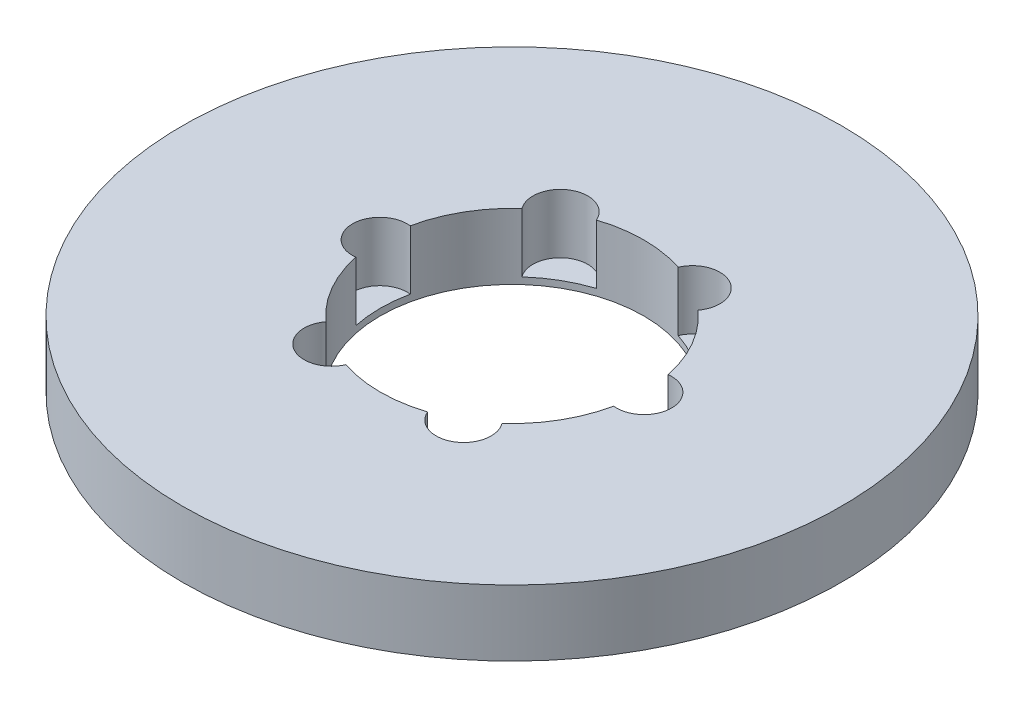
SolidWorks part; units mm, degrees
ref_plane "Front Plane" through (0, 0, 0) normal (0, 0, 1) x (1, 0, 0)
ref_plane "Top Plane" through (0, 0, 0) normal (0, 1, 0) x (1, 0, 0)
ref_plane "Right Plane" through (0, 0, 0) normal (1, 0, 0) x (0, 0, -1)
sketch "Sketch1" plane through (0, 0, 0) normal (0, 1, 0) x (1, 0, 0)
  circle A0 centre (0, 0) radius 75
  dimension "FLANGE_OD" = 150
extrude "Boss-Extrude1" add sketch "Sketch1" along normal blind 15
sketch "Sketch2" plane through (0, 0, 0) normal (0, 1, 0) x (1, 0, 0)
  circle A0 centre (0, 0) radius 30
  dimension "BORE_D" = 60
extrude "Cut-Extrude1" cut sketch "Sketch2" along normal through all
sketch "Sketch3" plane through (0, 15, 0) normal (0, 1, 0) x (1, 0, 0)
  circle A0 centre (0, 0) radius 30.0634 construction
  circle A1 centre (-30.0634, 0) radius 6.2463
  dimension "BOLT_D" = 12.4927
  dimension "BOLT_PCD" = 60.1268
extrude "Cut-Extrude2" cut sketch "Sketch3" against normal blind 13.483
pattern_circular "CirPattern1" count 6 over 360 about axis through (0, 0, 0) along (0, 1, 0) of "Cut-Extrude2"
